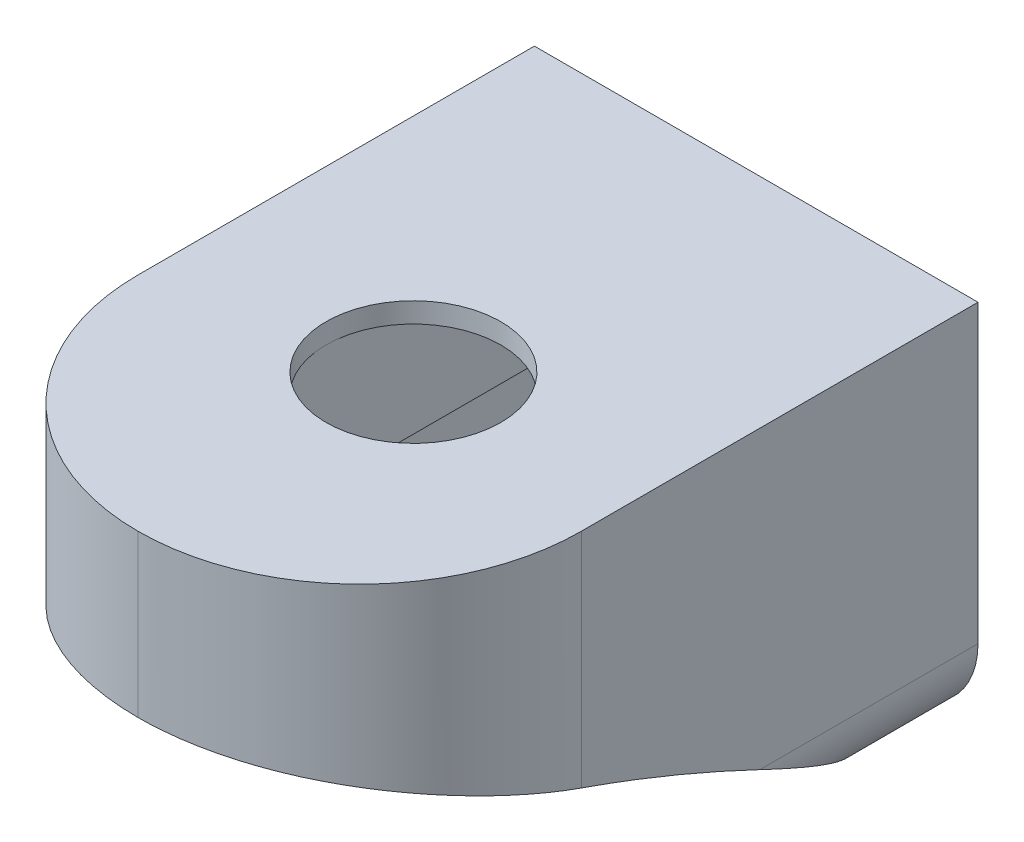
SolidWorks part; units mm, degrees
ref_plane "Front Plane" through (0, 0, 0) normal (0, 0, 1) x (1, 0, 0)
ref_plane "Top Plane" through (0, 0, 0) normal (0, 1, 0) x (1, 0, 0)
ref_plane "Right Plane" through (0, 0, 0) normal (1, 0, 0) x (0, 0, -1)
sketch "Sketch1" plane through (0, 0, 0) normal (0, 0, 1) x (1, 0, 0)
  line L1 (16.5, 14) -> (-16.5, 14)
  line L2 (16.5, 14) -> (16.5, -14)
  line L3 (16.5, -14) -> (-16.5, -14)
  line L4 (-16.5, 14) -> (-16.5, -14)
  line L5 (16.5, 14) -> (-16.5, -14) construction
  line L6 (16.5, -14) -> (-16.5, 14) construction
  point P0 (0, 0)
  dimension "D1" = 33
  dimension "D2" = 28
extrude "Boss-Extrude1" add sketch "Sketch1" along normal blind 46 contours L2 L1 L4 L3
sketch "Sketch2" plane through (16.5, 0, 0) normal (1, 0, 0) x (0, 0, -1)
  line L0 (-46, -14) -> (0, -14) construction
  line L1 (-46, 14) -> (-46, -14) construction
  line L2 (-46, 2) -> (-46, -14)
  line L3 (-46, -14) -> (-5, -14)
  line L4 (0, 14) -> (0, -14) construction
  line L5 (-46, 14) -> (0, 14) construction
  spline S0 degree 2 poles (-5, -14) (-24.4458, -2.4347) (-46, 2) knots 0 0 0 1 1 1
  dimension "D1" = 5
  dimension "D2" = 12
extrude "Cut-Extrude1" cut sketch "Sketch2" against normal through all
sketch "Sketch3" plane through (16.5, 0, 0) normal (1, 0, 0) x (0, 0, -1)
  line L0 (-5, -14) -> (-2.5, -14)
  line L1 (-5, -14) -> (0, -14) construction
  line L2 (-2.5, -14) -> (-2.5, 3.5)
  line L3 (-2.5, 3.5) -> (-40.5, 3.5)
  line L4 (-40.5, 3.5) -> (-40.5, 0.7437)
  parabola Q0 (-5, -14) -> (-46, 2) focus (-53.6889, -62.6693) apex (-35.3547, -0.663) construction
  parabola Q2 (-5, -14) -> (-46, 2) focus (-53.6889, -62.6693) apex (-35.3547, -0.663) construction
  parabola Q3 (-5, -14) -> (-40.5, 0.7437) focus (-53.6889, -62.6693) apex (-35.3547, -0.663)
  dimension "D1" = 17.5
  dimension "D2" = 38
extrude "Cut-Extrude2" cut sketch "Sketch3" against normal blind 27 from offset 3 offset against normal yes
fillet "Fillet1" radius 12.5 2 edges at (13.5, 2.1218, 40.5) (-13.5, 2.1218, 40.5)
fillet "Fillet2" radius 16.5 2 edges at (16.5, 8, 46) (-16.5, 8, 46)
fillet "Fillet3" radius 6 2 edges at (-16.5, -14, 2.5) (16.5, -14, 2.5)
sketch "Sketch4" plane through (0, 3.5, 0) normal (0, -1, 0) x (1, 0, 0)
  line L0 (0, 0) -> (0, 46) construction
  line L1 (-13.5, 2.5) -> (13.5, 2.5) construction
  line L2 (-6.5, 32) -> (6.5, 32)
  line L3 (-6.5, 32) -> (-6.5, 9)
  line L4 (-6.5, 9) -> (6.5, 9)
  line L5 (6.5, 32) -> (6.5, 9)
  line L6 (-6.5, 32) -> (6.5, 9) construction
  line L7 (-6.5, 9) -> (6.5, 32) construction
  point P4 (0, 20.5)
  dimension "D1" = 6.5
  dimension "D2" = 23
  dimension "D3" = 13
extrude "Cut-Extrude3" cut sketch "Sketch4" against normal blind 9
sketch "Sketch5" plane through (0, 12.5, 0) normal (0, -1, 0) x (1, 0, 0)
  line L0 (0, 32) -> (0, 9) construction
  line L1 (6.5, 32) -> (-6.5, 32) construction
  line L2 (-6.5, 9) -> (6.5, 9) construction
  circle A0 centre (0, 25.5) radius 6.5
  dimension "D1" = 13
extrude "Cut-Extrude4" cut sketch "Sketch5" against normal through all
sketch "Sketch6" plane through (0, 3.5, 0) normal (0, -1, 0) x (1, 0, 0)
  line L0 (-6.5, 20.5) -> (6.5, 20.5) construction
  line L1 (-6.5, 32) -> (-6.5, 9) construction
  line L2 (6.5, 9) -> (6.5, 32) construction
  line L3 (0, 34.3) -> (0, 6.7) construction
  circle A0 centre (0, 34.3) radius 1
  circle A1 centre (0, 6.7) radius 1
  point P10 (0, 20.5)
  dimension "D2" = 2
  dimension "D1" = 27.6
extrude "Cut-Extrude5" cut sketch "Sketch6" against normal blind 8
sketch "Sketch7" plane through (0, 0, 0) normal (0, 0, -1) x (-1, 0, 0)
  line L0 (0, 0) -> (-16.5, 0) construction
  line L1 (-16.5, 14) -> (-16.5, -8) construction
  circle A0 centre (-9.5, 0) radius 1.3
  circle A1 centre (-5, 0) radius 2.5
  circle A2 centre (-0.5, 0) radius 1.3
  dimension "D1" = 2.6
  dimension "D2" = 5
  dimension "D3" = 11.5
  dimension "D4" = 9
  dimension "D5" = 4.5
extrude "Cut-Extrude6" cut sketch "Sketch7" against normal up to surface (2.5 mm away) up to face at (0, -7.9645, 2.5)
